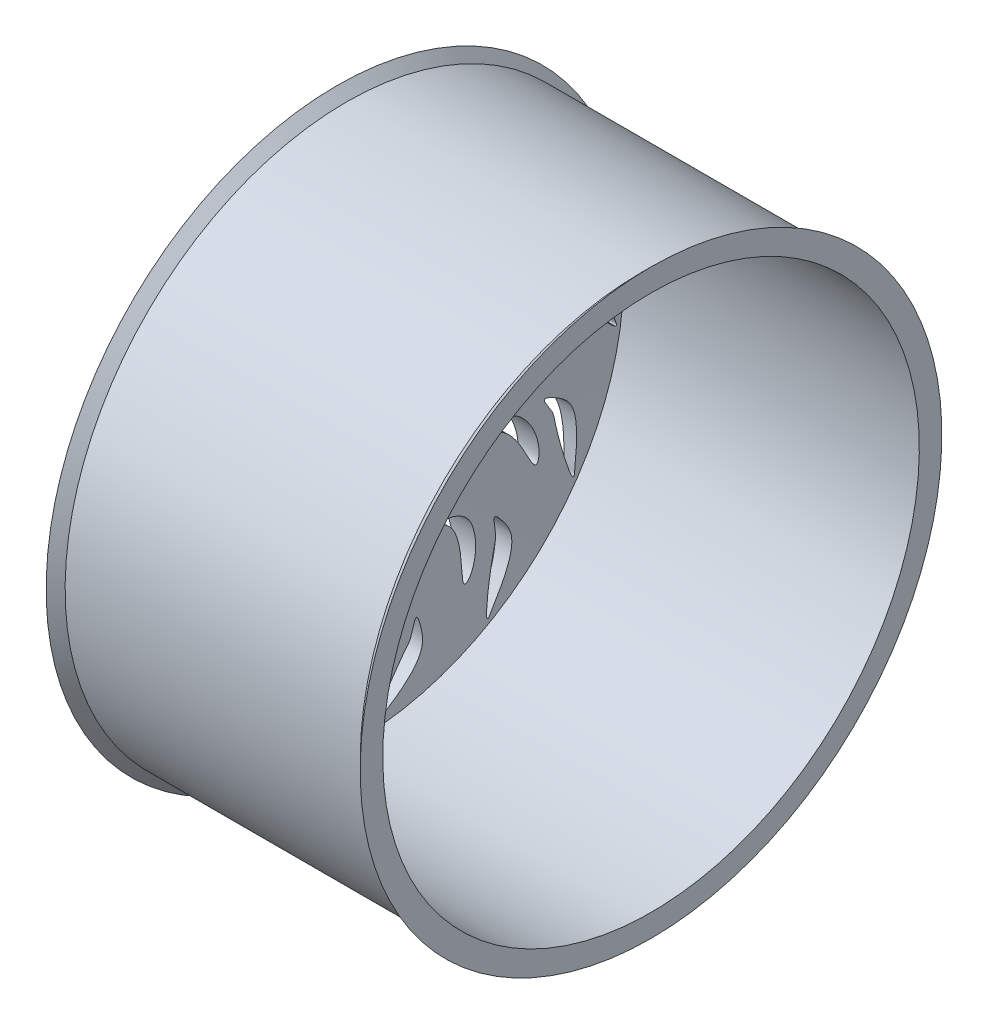
SolidWorks part; units mm, degrees
material "Chrome Stainless Steel"
ref_plane "Front Plane" through (0, 0, 0) normal (0, 0, 1) x (1, 0, 0)
ref_plane "Top Plane" through (0, 0, 0) normal (0, 1, 0) x (1, 0, 0)
ref_plane "Right Plane" through (0, 0, 0) normal (1, 0, 0) x (0, 0, -1)
sketch "Sketch2" plane through (0, 0, 0) normal (0, 0, 1) x (1, 0, 0)
  line L0 (-63.5, 0) -> (104.14, 0)
  line L1 (104.14, 0) -> (109.5282, 5.3882)
  line L2 (-63.5, 0) -> (-68.8882, 5.3882)
  line L3 (109.5282, 5.3882) -> (109.5282, -7.414)
  line L4 (-68.8882, 5.3882) -> (-68.8882, -5.3882)
  line L5 (-68.8882, -5.3882) -> (-63.5, -7.414)
  line L6 (106.4986, -159.814) -> (-106.8584, -159.814) construction
  line L7 (109.5282, -7.414) -> (-58.4673, -7.414)
  line L8 (-58.4673, -7.414) -> (-68.8882, -159.814)
  line L9 (-75.2289, -159.814) -> (-68.8882, -159.814)
  spline S0 degree 2 poles (-63.5, -7.414) (-97.6004, -104.3973) (-75.2289, -159.814) knots 0 0 0 0.818434 0.818434 0.818434
  dimension "D1" = 167.64
  dimension "D3" = 7.62
  dimension "D4" = 135
  dimension "D5" = 152.4
revolve "Revolve1" add sketch "Sketch2" angle 360 about L6
ref_plane "Plane1" through (-84.1282, 0, 0) normal (-1, 0, 0) x (0, 0, 1)
sketch "Sketch3" plane through (-84.1282, 0, 0) normal (-1, 0, 0) x (0, 0, 1)
  line L0 (-154.4259, -159.814) -> (154.4259, -159.814) construction
  line L1 (0, -7.414) -> (0, -314.2399) construction
  circle A0 centre (0, -159.814) radius 154.4259 construction
  circle A1 centre (0, -159.814) radius 152.4 construction
  circle A2 centre (0, -159.814) radius 25.4
  circle A3 centre (0, -159.814) radius 44.6214
  dimension "D1" = 50.8
extrude "Cut-Extrude3" cut sketch "Sketch3" against normal blind 25.4 draft 29 contours A3 A2
sketch "Sketch4" plane through (-84.1282, 0, 0) normal (-1, 0, 0) x (0, 0, 1)
  spline S0 degree 3 poles (17.2371, -13.7057) (4.2695, -4.0162) (25.5566, -32.0513) (35.0085, -41.7647) (37.354, -56.6582) (41.8405, -26.4027) (17.2371, -13.7057) (4.2695, -4.0162) (25.5566, -32.0513) knots -0.191148 -0.150727 -0.016747 0 0.536215 0.619467 0.808852 0.849273 0.983253 1 1.536215 1.619467 1.808852 only from (14.1022, -11.373) to (14.1022, -11.373)
  spline S1 degree 3 poles (28.0671, -66.139) (25.3422, -41.2575) (-2.3651, -23.2992) (24.0218, -56.8524) (13.2555, -73.7821) (28.0671, -66.139) (25.3422, -41.2575) (-2.3651, -23.2992) knots -0.261937 -0.224105 -0.02241 0 0.326478 0.738063 0.775895 0.97759 1 1.326478 1.738063 1.775895 only from (26.8017, -55.0297) to (26.8017, -55.0297)
  spline S2 degree 2 poles (10.9087, -74.7706) (22.9006, -96.975) (15.7127, -116.6986) knots 0 0 0 0.477785 0.477785 0.477785
  spline S3 degree 2 poles (15.7127, -116.6986) (45.1445, -89.2304) (10.9087, -74.7706) knots 0 0 0 1 1 1
extrude "Cut-Extrude4" cut sketch "Sketch4" against normal through all
pattern_circular "CirPattern1" count 14 over 360 about axis through (-84.1282, -159.814, 0) along (-1, 0, 0) of "Cut-Extrude4"
sketch "Sketch5" plane through (0, 0, 0) normal (1, 0, 0) x (0, 0, -1)
  circle A0 centre (0, -159.814) radius 12.7
  dimension "D1" = 25.4
extrude "Cut-Extrude5" cut sketch "Sketch5" against normal through all
